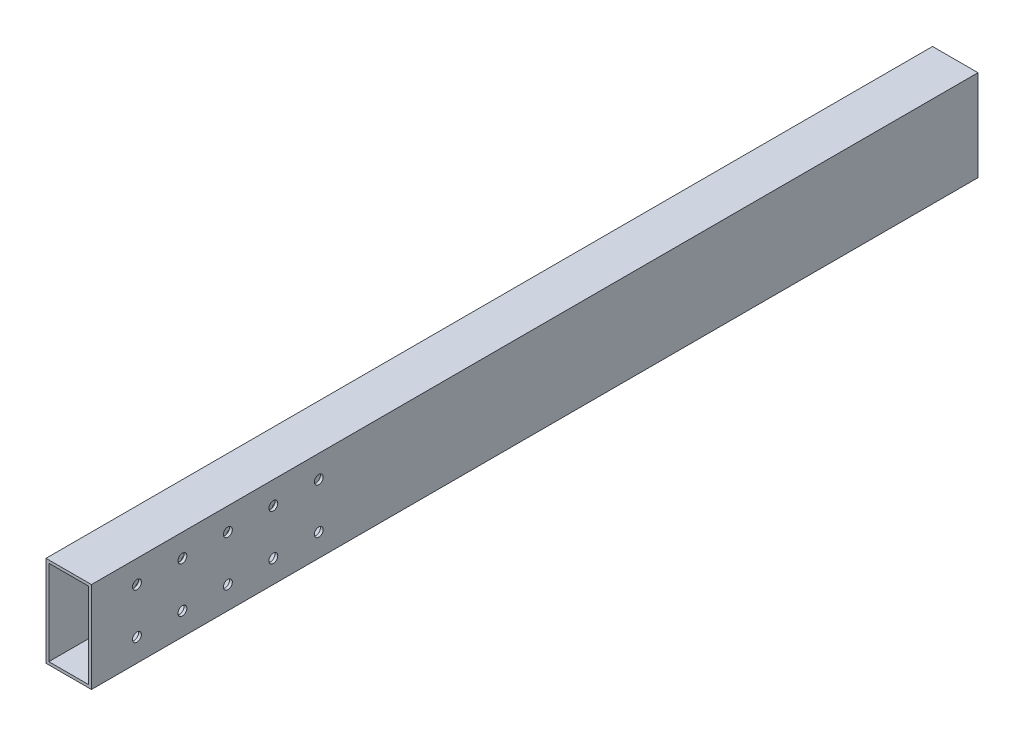
SolidWorks part; units mm, degrees
material "6061-T4 (SS)"
ref_plane "Front Plane" through (0, 0, 0) normal (0, 0, 1) x (1, 0, 0)
ref_plane "Top Plane" through (0, 0, 0) normal (0, 1, 0) x (1, 0, 0)
ref_plane "Right Plane" through (0, 0, 0) normal (1, 0, 0) x (0, 0, -1)
sketch "Sketch1" plane through (0, 0, 0) normal (0, 0, 1) x (1, 0, 0)
  line L0 (1.5875, 49.2125) -> (23.8125, 49.2125)
  line L5 (0, 0) -> (25.4, 0)
  line L6 (0, 0) -> (0, 50.8)
  line L7 (0, 50.8) -> (25.4, 50.8)
  line L8 (25.4, 0) -> (25.4, 50.8)
  line L13 (23.8125, 1.5875) -> (23.8125, 49.2125)
  line L14 (1.5875, 1.5875) -> (23.8125, 1.5875)
  line L15 (1.5875, 1.5875) -> (1.5875, 49.2125)
  dimension "D1" = 25.4
  dimension "D2" = 1.5875
  dimension "D3" = 50.8
extrude "Boss-Extrude1" add sketch "Sketch1" along normal blind 495.3
sketch "Sketch2" plane through (25.4, 0, 0) normal (-1, 0, 0) x (0, 0, 1)
  line L0 (495.3, 50.8) -> (495.3, 0) construction
  line L1 (495.3, 50.8) -> (0, 50.8) construction
  circle A16 centre (444.5, 38.1) radius 2.4892
  circle A17 centre (419.1, 38.1) radius 2.4892
  circle A18 centre (393.7, 38.1) radius 2.4892
  circle A19 centre (368.3, 38.1) radius 2.4892
  circle A21 centre (444.5, 12.7) radius 2.4892
  circle A22 centre (419.1, 12.7) radius 2.4892
  circle A23 centre (393.7, 12.7) radius 2.4892
  circle A24 centre (368.3, 12.7) radius 2.4892
  circle A26 centre (469.9, 12.7) radius 2.4892
  circle A29 centre (469.9, 38.1) radius 2.4892
  circle A30 centre (342.9, 38.1) radius 2.4892 [skipped]
  circle A31 centre (342.9, 12.7) radius 2.4892 [skipped]
  dimension "D4" = 25.4
  dimension "D5" = 6
  dimension "D6" = 2
  dimension "D1" = 4.9784
  dimension "D7" = 12.7
  dimension "D2" = 25.4
  dimension "D3" = 25.4
extrude "Cut-Extrude1" cut sketch "Sketch2" along normal up to next contours A24 | A23 | A18 | A19
sketch "Sketch3" plane through (0, 0, 0) normal (-1, 0, 0) x (0, 0, 1)
  line L0 (495.3, 25.4) -> (0, 25.4) construction
  line L1 (495.3, 50.8) -> (495.3, 0) construction
  line L2 (0, 50.8) -> (0, 0) construction
  line L4 (88.9, 41.275) -> (139.7, 41.275) construction
  line L5 (88.9, 41.275) -> (88.9, 9.525) construction
  line L6 (88.9, 9.525) -> (139.7, 9.525) construction
  line L7 (139.7, 41.275) -> (139.7, 9.525) construction
  line L8 (88.9, 41.275) -> (139.7, 9.525) construction
  line L9 (88.9, 9.525) -> (139.7, 41.275) construction
  circle A0 centre (114.3, 25.4) radius 14.2875
  circle A1 centre (139.7, 41.275) radius 2.4892
  circle A2 centre (88.9, 41.275) radius 2.4892
  circle A3 centre (88.9, 9.525) radius 2.4892
  circle A4 centre (139.7, 9.525) radius 2.4892
  dimension "D1" = 28.575
  dimension "D2" = 114.3
  dimension "D5" = 4.9784
  dimension "D3" = 15.875
  dimension "D4" = 25.4
extrude "Cut-Extrude2" cut sketch "Sketch3" against normal up to next
extrude "Cut-Extrude5" cut sketch "Sketch2<3>" along normal through all contours A22 | A17 | A26 | A29 | A16 | A21 | A23 | A19 | A24 | A18 region at (25.4, 38.1, 444.5) region at (25.4, 38.1, 419.1) region at (25.4, 38.1, 393.7) region at (25.4, 38.1, 368.3) region at (25.4, 12.7, 444.5) region at (25.4, 12.7, 419.1) region at (25.4, 12.7, 393.7) region at (25.4, 12.7, 368.3) region at (25.4, 12.7, 469.9) region at (25.4, 38.1, 469.9)
sketch "Sketch2<3>" plane through (25.4, 0, 0) normal (-1, 0, 0) x (0, 0, 1) same geometry as "Sketch2"
sketch "Sketch4" plane through (0, 0, 0) normal (-1, 0, 0) x (0, 0, 1)
  line L0 (0, 50.8) -> (0, 0) construction
  line L2 (495.3, 0) -> (0, 0) construction
  circle A0 centre (12.7, 38.1) radius 2.4892
  circle A1 centre (25.4, 38.1) radius 2.4892
  circle A2 centre (38.1, 38.1) radius 2.4892
  circle A3 centre (25.4, 12.7) radius 2.4892
  circle A4 centre (38.1, 12.7) radius 2.4892
  circle A5 centre (12.7, 12.7) radius 2.4892
  dimension "D1" = 4.9784
  dimension "D7" = 12.7
  dimension "D4" = 25.4
  dimension "D5" = 12.7
  dimension "D6" = 12.7
  dimension "D2" = 3
  dimension "D3" = 2
extrude "Cut-Extrude6" cut sketch "Sketch4" against normal up to next
